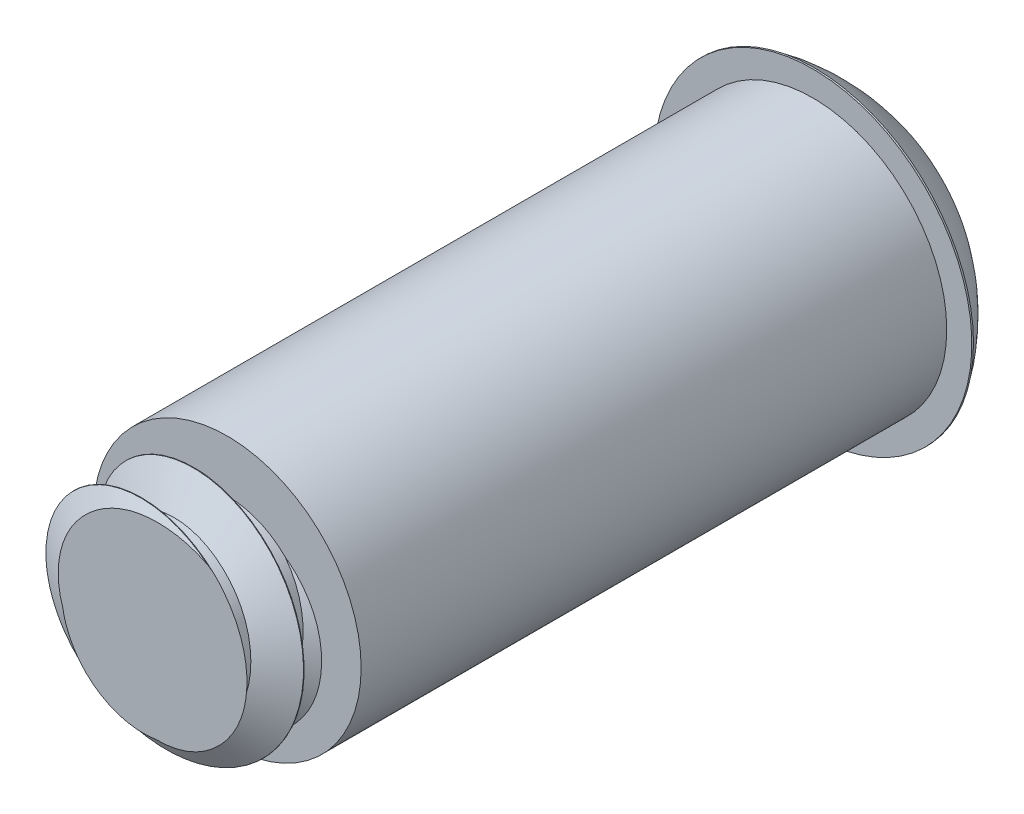
SolidWorks part; units mm, degrees
ref_plane "Front Plane" through (0, 0, 0) normal (0, 0, 1) x (1, 0, 0)
ref_plane "Top Plane" through (0, 0, 0) normal (0, 1, 0) x (1, 0, 0)
ref_plane "Right Plane" through (0, 0, 0) normal (1, 0, 0) x (0, 0, -1)
sketch "Sketch1" plane through (0, 0, 0) normal (0, 0, 1) x (1, 0, 0)
  circle A0 centre (0, 0) radius 1.7526
curve "Helix/Spiral1" pitch 0.7937 height 5.08 radius 1.7526 left hand yes centre (0, 0, 0) axis (0, 0, 1) start towards (0, 1, 0)
sketch "Sketch2" plane through (0, 0, 0) normal (0, 0, 1) x (1, 0, 0)
  circle A0 centre (0, 0) radius 1.7526
extrude "Boss-Extrude1" add sketch "Sketch2" along normal blind 1.27
sketch "Sketch3" plane through (0, 0, 0) normal (1, 0, 0) x (0, 0, -1)
  line L0 (-0.3925, 1.7526) -> (-0.0992, 1.2446)
  line L1 (-0.0992, 1.2446) -> (0.0992, 1.2446)
  line L2 (0.0992, 1.2446) -> (0.3925, 1.7526)
  line L3 (0.3925, 1.7526) -> (-0.3925, 1.7526)
  line L4 (0, 1.7526) -> (0, 1.2446) construction
  dimension "D1" = 60
  dimension "D2" = 0.508
  dimension "D3" = 0.1984
sweep "Cut-Sweep1" cut profiles "Sketch3" path "Helix/Spiral1" align with end faces yes
sketch "Sketch4" plane through (0, 0, 0) normal (0, 0, 1) x (1, 0, 0)
  circle A0 centre (0, 0) radius 2.032
extrude "Boss-Extrude2" add sketch "Sketch4" against normal blind 8.89
sketch "Sketch5" plane through (0, 0, -8.89) normal (0, 0, -1) x (-1, 0, 0)
  circle A0 centre (0, 0) radius 2.413
extrude "Boss-Extrude3" add sketch "Sketch5" along normal blind 0.0254
dome "Dome1" faces to dome 1 distance 1.27 reverse direction no elliptical dome no face at (-2.413, 0, -8.9154) parameters "D1"=1.27
